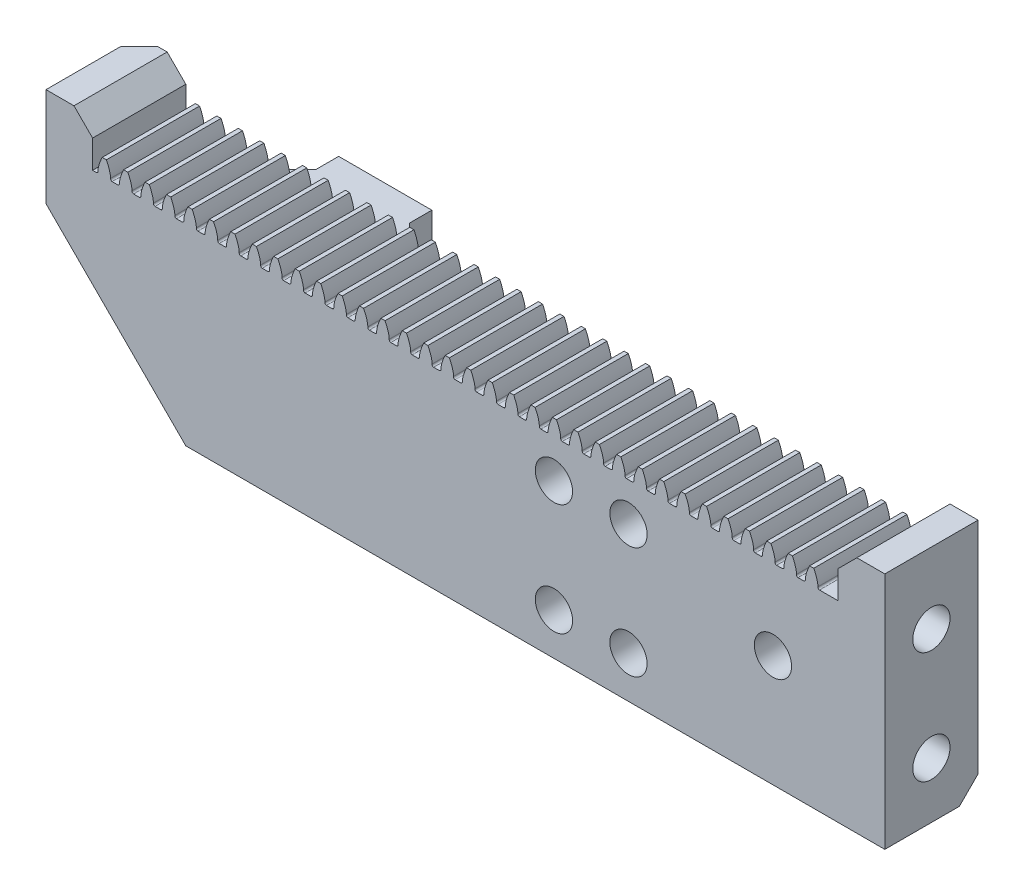
SolidWorks part; units mm, degrees
other "Uwaga1"
sketch "Szkic13" plane through (31.5, -10.5, 10) normal (0.379, -0.4248, 0.8222) x (0.8677, 0.4718, -0.1562)
material "ABS"
ref_plane "Płaszczyzna przednia" through (0, 0, 0) normal (0, 0, 1) x (1, 0, 0)
ref_plane "Płaszczyzna górna" through (0, 0, 0) normal (0, 1, 0) x (1, 0, 0)
ref_plane "Płaszczyzna prawa" through (0, 0, 0) normal (1, 0, 0) x (0, 0, -1)
sketch "Szkic1" plane through (0, 0, 0) normal (0, 0, 1) x (1, 0, 0)
  line L1 (-11.5, -8.5) -> (11.5, -8.5)
  line L2 (-11.5, -8.5) -> (-11.5, 8.5)
  line L3 (-11.5, 8.5) -> (11.5, 8.5)
  line L4 (11.5, -8.5) -> (11.5, 8.5)
  line L5 (-11.5, -8.5) -> (11.5, 8.5) construction
  line L6 (-11.5, 8.5) -> (11.5, -8.5) construction
  line L7 (-11.5, 8.5) -> (11.5, 8.5)
  line L8 (-11.5, 8.5) -> (-11.5, 10.1)
  line L9 (-11.5, 10.1) -> (11.5, 10.1)
  line L10 (11.5, 8.5) -> (11.5, 10.1)
  line L11 (11.5, -8.5) -> (31.5, -8.5)
  line L12 (11.5, -8.5) -> (11.5, 10.1)
  line L13 (11.5, 10.1) -> (31.5, 10.1)
  line L14 (31.5, -8.5) -> (31.5, 10.1)
  line L15 (-11.5, 10.1) -> (-58.5, 10.1)
  line L16 (-11.5, 10.1) -> (-11.5, -8.5)
  line L17 (-11.5, -8.5) -> (-58.5, -8.5)
  line L18 (-58.5, 10.1) -> (-58.5, -8.5)
  point P0 (0, 0)
  dimension "D1" = 17
  dimension "D2" = 23
  dimension "D3" = 1.6
  dimension "D4" = 23
  dimension "D5" = 18.6
  dimension "D6" = 20
  dimension "D7" = 18.6
  dimension "D8" = 47
extrude "Dodanie-wyciągnięcie1" add sketch "Szkic1" along normal blind 10 contours L1 L4 L3 L2 | L3 L10 L9 L8 | L11 L14 L13 L10 L4 | L15 L18 L17 L2 L8
sketch "Szkic2" plane through (0, 0, 10) normal (0, 0, 1) x (1, 0, 0)
  line L0 (0, 0) -> (-8.8665, 0) construction
  line L2 (0, 0) -> (0, 7.3642) construction
  circle A0 centre (-4, 6) radius 1.25
  circle A1 centre (4, 6) radius 1.25
  circle A2 centre (-4, -6) radius 1.25
  circle A3 centre (4, -6) radius 1.25
  dimension "D1" = 2.5
  dimension "D2" = 8
  dimension "D3" = 12
extrude "Wytnij-wyciągnięcie1" cut sketch "Szkic2" against normal blind 10
sketch "Szkic3" plane through (0, 0, 10) normal (0, 0, 1) x (1, 0, 0)
  circle A0 centre (-4, 6) radius 2
  circle A1 centre (4, 6) radius 2
  circle A2 centre (4, -6) radius 2
  circle A3 centre (-4, -6) radius 2
  dimension "D1" = 4
extrude "Wytnij-wyciągnięcie2" cut sketch "Szkic3" against normal blind 7
sketch "Szkic4" plane through (0, 0, 10) normal (0, 0, 1) x (1, 0, 0)
  line L0 (24.3269, 10.2979) -> (24.3285, 10.3258)
  line L1 (22.9801, 10.3241) -> (22.9818, 10.2962)
  line L2 (22.8093, 10.0979) -> (24.5, 10.1)
  line L3 (24.5, 10.1) -> (24.5, 3.1) construction
  line L4 (-58.5, 10.1) -> (31.5, 10.1) construction
  line L5 (-58.5, 10.1) -> (31.5, 10.1)
  line L6 (31.5, -8.5) -> (31.5, 10.1) construction
  arc A1 (24.3269, 10.2979) -> (24.5, 10.1) centre (24.5141, 10.287) ccw
  arc A2 (23.878, 11.8171) -> (23.427, 11.8165) centre (23.6685, -0.9312) ccw
  arc A3 (22.8093, 10.0979) -> (22.9818, 10.2962) centre (22.7947, 10.2848) ccw
  spline S0 degree 4 poles (24.3285, 10.3258) (24.3289, 10.3341) (24.3292, 10.3575) (24.3276, 10.4017) (24.3221, 10.4738) (24.3105, 10.5653) (24.2904, 10.6831) (24.2601, 10.8209) (24.2201, 10.9711) (24.1691, 11.1329) (24.1119, 11.2927) (24.049, 11.4504) (23.9829, 11.6013) (23.9305, 11.712) (23.8949, 11.7836) (23.878, 11.8171) knots 0 0 0 0 0 0.005377 0.015084 0.028532 0.04661 0.064855 0.092111 0.119476 0.146842 0.174209 0.201575 0.228941 0.253142 0.253142 0.253142 0.253142 0.253142
  spline S1 degree 4 poles (23.427, 11.8165) (23.4101, 11.783) (23.3747, 11.7113) (23.3225, 11.6005) (23.2569, 11.4494) (23.1943, 11.2915) (23.1375, 11.1316) (23.087, 10.9696) (23.0473, 10.8193) (23.0174, 10.6815) (22.9976, 10.5637) (22.9862, 10.4721) (22.9808, 10.4) (22.9794, 10.3558) (22.9798, 10.3324) (22.9801, 10.3241) knots 0 0 0 0 0 0.024201 0.051567 0.078933 0.1063 0.133666 0.161032 0.188287 0.206532 0.22461 0.238059 0.247765 0.253142 0.253142 0.253142 0.253142 0.253142
  dimension "D1" = 7
extrude "Dodanie-wyciągnięcie2" add sketch "Szkic4" against normal blind 10
pattern_linear "Szyk liniowy1" count 36 spacing 2.3 along (1, 0, 0) of "Dodanie-wyciągnięcie2"
sketch "Szkic5" plane through (0, -8.5, 0) normal (0, -1, 0) x (1, 0, 0)
  line L4 (-58.5, 0) -> (31.5, 0)
  line L5 (31.5, 0) -> (31.5, 10)
  line L6 (31.5, 10) -> (-58.5, 10)
  line L7 (31.5, 0) -> (31.5, 10)
  line L8 (-58.5, 0) -> (31.5, 0)
  line L10 (31.5, 10) -> (-58.5, 10)
  line L12 (-58.5, 10) -> (-58.5, 0)
  line L13 (-58.5, 10) -> (-58.5, 0)
  dimension "D1" = 0
extrude "Dodanie-wyciągnięcie3" add sketch "Szkic5" along normal blind 2
sketch "Szkic7" plane through (0, 10.1, 0) normal (0, 1, 0) x (1, 0, 0)
  line L1 (-58.5, 0) -> (-53.5, 0)
  line L2 (-58.5, 0) -> (-58.5, -10)
  line L3 (-58.5, -10) -> (-53.5, -10)
  line L4 (-53.5, 0) -> (-53.5, -10)
  line L5 (-57.6736, -10) -> (-58.5, -10) construction
  line L7 (31.5, 0) -> (26.5, 0)
  line L8 (31.5, 0) -> (31.5, -10)
  line L9 (31.5, -10) -> (26.5, -10)
  line L10 (26.5, 0) -> (26.5, -10)
  line L11 (31.5, -10) -> (24.5, -10) construction
  dimension "D1" = 10
  dimension "D2" = 5
  dimension "D3" = 10
  dimension "D4" = 5
extrude "Dodanie-wyciągnięcie5" add sketch "Szkic7" along normal blind 5
chamfer "Sfazowanie1" distance 2 angle 45 2 edges at (-53.5, 15.1, 5) (26.5, 15.1, 5)
sketch "Szkic8" plane through (31.5, 0, 0) normal (1, 0, 0) x (0, 0, -1)
  line L0 (0, -10.5) -> (-10, -10.5) construction
  circle A0 centre (-5, -4.5) radius 2
  circle A1 centre (-5, 7.5) radius 2
  point P4 (0, 0)
  point P7 (-5, -10.5)
  dimension "D1" = 6
  dimension "D3" = 4
  dimension "D2" = 12
extrude "Wytnij-wyciągnięcie3" cut sketch "Szkic8" against normal blind 8
sketch "Szkic9" plane through (23.5, 0, 0) normal (1, 0, 0) x (0, 0, -1)
  circle A0 centre (-5, 7.5) radius 1.5
  circle A1 centre (-5, -4.5) radius 1.5
  dimension "D1" = 3
  dimension "D2" = 3
extrude "Wytnij-wyciągnięcie4" cut sketch "Szkic9" against normal blind 5
sketch "Szkic10" plane through (0, 0, 10) normal (0, 0, 1) x (1, 0, 0)
  line L0 (31.5, -10.5) -> (-58.5, -10.5) construction
  line L1 (31.5, -10.5) -> (31.5, 15.1) construction
  circle A0 centre (19.5, 1.5) radius 2
  dimension "D1" = 4
  dimension "D2" = 12
  dimension "D3" = 12
extrude "Wytnij-wyciągnięcie5" cut sketch "Szkic10" against normal blind 8
sketch "Szkic11" plane through (0, 0, 0) normal (0, 0, -1) x (-1, 0, 0)
  line L1 (43.5, 4.2) -> (33.5, 4.2)
  line L2 (43.5, 4.2) -> (43.5, 8.2)
  line L3 (43.5, 8.2) -> (33.5, 8.2)
  line L4 (33.5, 4.2) -> (33.5, 8.2)
  line L5 (58.5, 15.1) -> (58.5, -10.5) construction
  line L6 (58.5, -10.5) -> (-31.5, -10.5) construction
  point P8 (0, 0)
  dimension "D1" = 4
  dimension "D2" = 10
  dimension "D3" = 15
  dimension "D4" = 14.7
extrude "Dodanie-wyciągnięcie6" add sketch "Szkic11" along normal blind 4.4
sketch "Szkic12" plane through (0, 0, -4.4) normal (0, 0, -1) x (-1, 0, 0)
  line L1 (33.5, 8.2) -> (43.5, 8.2)
  line L2 (33.5, 8.2) -> (33.5, 2.6)
  line L3 (33.5, 2.6) -> (43.5, 2.6)
  line L4 (43.5, 8.2) -> (43.5, 2.6)
  dimension "D1" = 5.6
  dimension "D2" = 10
extrude "Dodanie-wyciągnięcie7" add sketch "Szkic12" along normal blind 2
chamfer "Sfazowanie2" distance 4 angle 45 2 edges at (-33.5, 6.2, 0) (-43.5, 6.2, 0)
chamfer "Sfazowanie3" distance 1 angle 45 6 edges at (-38.5, 4.2, 0) (-38.5, 2.6, -4.4) (-43.5, 2.6, -5.4) (-38.5, 2.6, -6.4) (-33.5, 2.6, -5.4) (-38.5, 8.2, 0)
chamfer "Sfazowanie4" distance 15 angle 45 1 edges at (-58.5, -10.5, 5)
chamfer "Sfazowanie5" distance 2 angle 45 3 edges at (-6, -10.5, 0) (-51, -3, 0) (-58.5, 9.8, 0)
